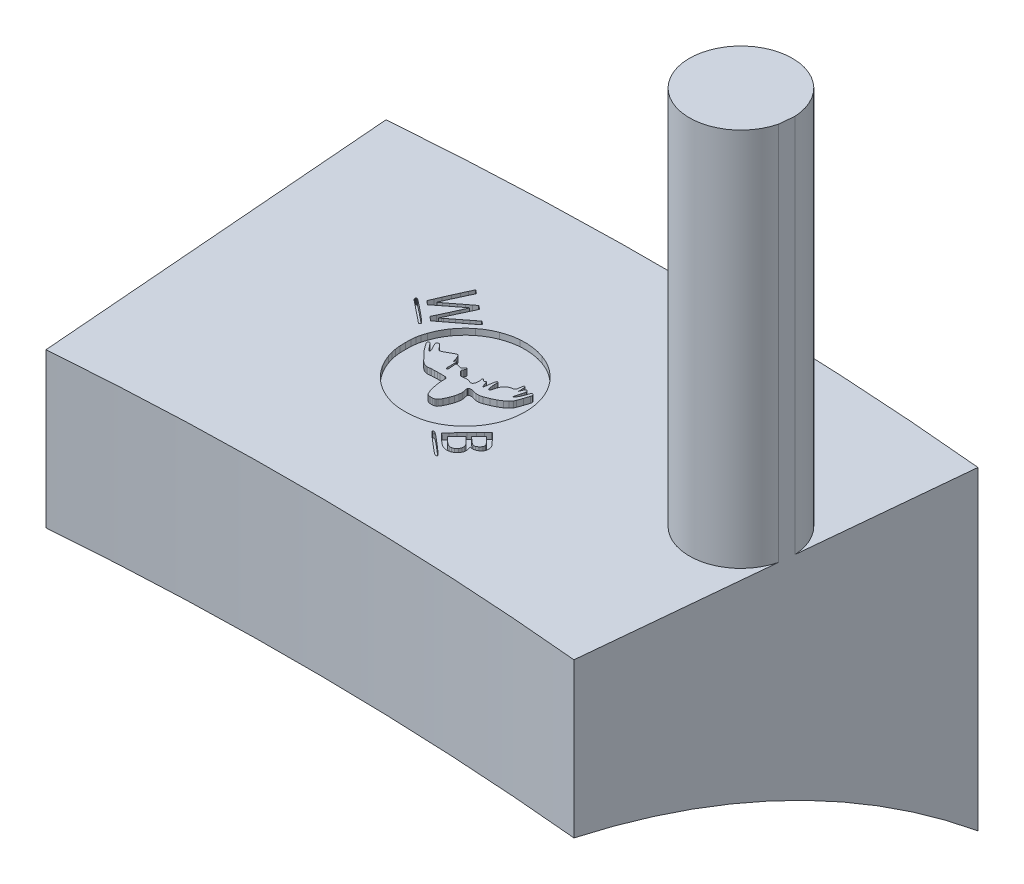
SolidWorks part; units mm, degrees
ref_plane "Front Plane" through (0, 0, 0) normal (0, 0, 1) x (1, 0, 0)
ref_plane "Top Plane" through (0, 0, 0) normal (0, 1, 0) x (1, 0, 0)
ref_plane "Right Plane" through (0, 0, 0) normal (1, 0, 0) x (0, 0, -1)
sketch "Sketch1" plane through (0, 0, 0) normal (0, 1, 0) x (1, 0, 0)
  circle A0 centre (0, 0) radius 140.97
  circle A1 centre (0, 0) radius 125.73
  dimension "D1" = 281.94
  dimension "D2" = 251.46
extrude "Boss-Extrude1" add sketch "Sketch1" along normal blind 12.954
sketch "Sketch3" plane through (0, 12.954, 0) normal (0, 1, 0) x (1, 0, 0)
  line L0 (0, 0) -> (13.4916, 140.3229)
  line L1 (13.4916, 140.3229) -> (0, 0)
  line L2 (0, 0) -> (-11.0802, 140.5339)
  circle A0 centre (0, 0) radius 140.97 construction
  circle A1 centre (0, 0) radius 140.97
  circle M3 centre (0, 0) radius 140.97
  circle M4 centre (0, 0) radius 125.73
  dimension "D1" = 10
extrude "Cut-Extrude1" cut sketch "Sketch3" against normal blind 12.954 contours L0 L2 M4 | L2 L0 M4 M3 region at (-0.0205, 12.954, 2.3917) region at (16.7282, 12.954, -132.3566)
sketch "Sketch5" plane through (0, 0, 0) normal (0, 1, 0) x (1, 0, 0)
  line L0 (-9.8823, 125.341) -> (-11.0802, 140.5339) construction
  line L1 (12.033, 125.1529) -> (13.4916, 140.3229) construction
  arc A1 (-10.4813, 132.9374) -> (12.7623, 132.7379) centre (0, 0) cw
  circle A2 centre (10.7123, 133.3451) radius 2.1209
  dimension "D1" = 4.2418
  dimension "D2" = 2.05
  dimension "D3" = 133.35
extrude "Boss-Extrude2" add sketch "Sketch5" along normal blind 28.575 contours A2
sketch "Sketch2" plane through (0, 0, 0) normal (0, 0, 1) x (1, 0, 0)
  line L0 (0, 12.954) -> (-125.73, 12.954)
  line L1 (13.4916, 12.954) -> (-11.0802, 12.954) construction
  line L2 (-125.73, 12.954) -> (-125.73, 6.604)
  line L3 (-125.73, 6.604) -> (-125.73, 0)
  line L4 (-125.73, 0) -> (-140.97, 0)
  line L5 (0, 0) -> (0, 30.8515)
  arc A0 (-125.73, 6.604) -> (-140.97, 0) centre (-121.1655, -24.8162) ccw
  dimension "D3" = 31.75
  dimension "D1" = 125.73
  dimension "D2" = 6.35
revolve "Cut-Revolve1" cut sketch "Sketch2" angle 360 about L5
sketch "Sketch6" plane through (0, 0, 0) normal (0.9954, 0, 0.0957) x (0.0957, 0, -0.9954)
  line L1 (114.9487, -1.4366) -> (150.8904, -1.4366)
  line L2 (114.9487, -1.4366) -> (114.9487, 48.5634)
  line L3 (114.9487, 48.5634) -> (150.8904, 48.5634)
  line L4 (150.8904, -1.4366) -> (150.8904, 48.5634)
  dimension "D1" = 50
extrude "Cut-Extrude2" cut sketch "Sketch6" along normal blind 25.4
sketch "Sketch7" plane through (0, 12.954, 0) normal (0, 1, 0) x (1, 0, 0)
  line L0 (-3.7053, 134.8491) -> (-3.6341, 134.7927)
  line L1 (-3.6341, 134.7927) -> (-3.1603, 135.1619)
  line L2 (-3.1603, 135.1619) -> (-2.9772, 135.3047)
  line L3 (-2.9772, 135.3047) -> (-2.8193, 135.4277)
  line L4 (-2.8193, 135.4277) -> (-2.6815, 135.5351)
  line L5 (-2.6815, 135.5351) -> (-2.6645, 135.5483)
  line L6 (-3.081, 134.6146) -> (-3.1693, 134.4272)
  line L7 (-3.1693, 134.4272) -> (-3.0827, 134.3548)
  line L8 (-3.0827, 134.3548) -> (-2.9962, 134.2823)
  line L9 (-2.9962, 134.2823) -> (-2.4199, 134.7222)
  line L10 (-2.6915, 134.7377) -> (-2.8183, 134.6385)
  line L11 (-2.8652, 134.6025) -> (-2.9338, 134.5503)
  line L12 (-2.9338, 134.5503) -> (-2.8718, 134.6853)
  line L13 (-2.8359, 134.7632) -> (-2.7678, 134.9098)
  line L14 (-2.7678, 134.9098) -> (-2.6878, 135.0818)
  line L15 (-2.6878, 135.0818) -> (-2.6046, 135.26)
  line L16 (-2.6046, 135.26) -> (-2.3995, 135.6997)
  line L17 (-2.3995, 135.6997) -> (-2.4697, 135.7591)
  line L18 (-3.3944, 135.1758) -> (-3.5283, 135.0739)
  line L19 (-3.534, 135.0793) -> (-3.4641, 135.2346)
  line L20 (-3.2799, 135.6368) -> (-3.0213, 136.1941)
  line L21 (-3.0213, 136.1941) -> (-3.0907, 136.254)
  line L22 (-3.1779, 136.3098) -> (-3.2698, 136.1122)
  line L23 (1.3179, 133.7284) -> (1.327, 133.5741)
  line L24 (1.327, 133.5741) -> (1.3617, 133.6657)
  line L25 (-1.9323, 133.5887) -> (-1.9076, 133.5586)
  line L26 (-1.9076, 133.5586) -> (-1.8767, 133.521)
  line L27 (-1.8767, 133.521) -> (-1.8472, 133.485)
  line L28 (-0.9298, 133.0884) -> (-0.9418, 133.2717)
  line L29 (-0.9418, 133.2717) -> (-0.8956, 133.2717)
  line L30 (-0.5709, 133.2146) -> (-0.6086, 133.1406)
  line L31 (-0.6086, 133.1406) -> (-0.5415, 133.0587)
  line L32 (2.3359, 130.5324) -> (2.3094, 130.596)
  line L33 (2.3094, 130.596) -> (2.4047, 130.5856)
  line L34 (2.2433, 131.5638) -> (2.0938, 131.4139)
  line L35 (2.0965, 130.8858) -> (1.9736, 131.0016)
  line L36 (1.9736, 131.0016) -> (2.0164, 131.0508)
  line L37 (1.6081, 130.3734) -> (1.4737, 130.5022)
  line L38 (1.4737, 130.5022) -> (1.6657, 130.6956)
  line L39 (1.6657, 130.6956) -> (1.8577, 130.8889)
  line L40 (1.8577, 130.8889) -> (1.9656, 130.7837)
  arc A0 (-3.4904, 135.6272) -> (-3.6076, 135.3626) centre (27.6931, 121.6549) ccw
  arc A1 (-3.6076, 135.3626) -> (-3.7046, 135.137) centre (12.6966, 128.2224) ccw
  arc A2 (-3.7046, 135.137) -> (-3.7885, 134.9374) centre (82.6018, 98.751) ccw
  arc A3 (-3.7885, 134.9374) -> (-3.7873, 134.9229) centre (-3.7738, 134.9313) ccw
  arc A4 (-3.7873, 134.9229) -> (-3.7794, 134.9132) centre (-3.7452, 134.9489) ccw
  arc A5 (-3.7794, 134.9132) -> (-3.7588, 134.894) centre (-3.121, 135.602) ccw
  arc A6 (-3.7588, 134.894) -> (-3.7334, 134.8719) centre (-3.1178, 135.6055) ccw
  arc A7 (-3.7334, 134.8719) -> (-3.7053, 134.8491) centre (-2.9112, 135.8517) ccw
  arc A8 (-2.6578, 135.5431) -> (-2.6645, 135.5483) centre (-2.6618, 135.5449) ccw
  arc A9 (-2.7745, 135.2804) -> (-2.6578, 135.5431) centre (-77.3531, 168.543) ccw
  arc A10 (-2.9131, 134.9747) -> (-2.7745, 135.2804) centre (-26.7146, 145.9578) ccw
  arc A11 (-3.081, 134.6146) -> (-2.9131, 134.9747) centre (-49.4562, 156.4518) ccw
  arc A12 (-2.4199, 134.7222) -> (-2.197, 134.8928) centre (-70.4269, 223.8204) ccw
  arc A13 (-2.197, 134.8928) -> (-2.0048, 135.0409) centre (-40.4648, 184.7692) ccw
  arc A14 (-2.0048, 135.0409) -> (-1.8382, 135.1699) centre (-111.6015, 276.7477) ccw
  arc A15 (-1.8382, 135.1699) -> (-1.816, 135.1893) centre (-1.9902, 135.366) ccw
  arc A16 (-1.816, 135.1893) -> (-1.804, 135.2061) centre (-1.8581, 135.232) ccw
  arc A17 (-1.804, 135.2061) -> (-1.8039, 135.2208) centre (-1.8197, 135.2136) ccw
  arc A18 (-1.8039, 135.2208) -> (-1.8165, 135.2382) centre (-1.853, 135.1984) ccw
  arc A19 (-1.8165, 135.2382) -> (-1.8527, 135.2698) centre (-2.4989, 134.4947) ccw
  arc A20 (-1.8527, 135.2698) -> (-1.8782, 135.2903) centre (-2.4241, 134.5844) ccw
  arc A21 (-1.8782, 135.2903) -> (-1.902, 135.3077) centre (-2.2326, 134.8321) ccw
  arc A22 (-1.902, 135.3077) -> (-1.9222, 135.3212) centre (-2.2752, 134.7707) ccw
  arc A23 (-1.9222, 135.3212) -> (-1.9303, 135.3238) centre (-1.9309, 135.3076) ccw
  arc A24 (-1.9303, 135.3238) -> (-1.94, 135.3207) centre (-1.9309, 135.3087) ccw
  arc A25 (-1.94, 135.3207) -> (-2.0651, 135.2258) centre (61.9876, 50.9611) ccw
  arc A26 (-2.0651, 135.2258) -> (-2.2057, 135.1178) centre (8.9255, 120.7671) ccw
  arc A27 (-2.2057, 135.1178) -> (-2.3702, 134.9895) centre (19.016, 107.7582) ccw
  arc A28 (-2.5385, 134.8574) -> (-2.3702, 134.9895) centre (-141.7495, 312.4628) ccw
  arc A29 (-2.6915, 134.7377) -> (-2.5385, 134.8574) centre (-97.35, 255.8182) ccw
  arc A30 (-2.8652, 134.6025) -> (-2.8183, 134.6385) centre (-5.5175, 138.0943) ccw
  arc A31 (-2.8359, 134.7632) -> (-2.8718, 134.6853) centre (16.7108, 125.6919) ccw
  arc A32 (-2.4697, 135.7591) -> (-2.4976, 135.7819) centre (-3.1441, 134.9621) ccw
  arc A33 (-2.4976, 135.7819) -> (-2.5233, 135.8012) centre (-2.9068, 135.263) ccw
  arc A34 (-2.5233, 135.8012) -> (-2.5452, 135.8163) centre (-2.9811, 135.1588) ccw
  arc A35 (-2.5452, 135.8163) -> (-2.5535, 135.8188) centre (-2.5538, 135.8033) ccw
  arc A36 (-2.5535, 135.8188) -> (-2.5632, 135.8157) centre (-2.5538, 135.8033) ccw
  arc A37 (-2.5632, 135.8157) -> (-2.7041, 135.7088) centre (89.1723, 14.6991) ccw
  arc A38 (-2.7041, 135.7088) -> (-2.8622, 135.5877) centre (11.3945, 117.1401) ccw
  arc A39 (-2.8622, 135.5877) -> (-3.0473, 135.4439) centre (24.4097, 100.2988) ccw
  arc A40 (-3.2319, 135.3004) -> (-3.0473, 135.4439) centre (-33.5628, 174.5039) ccw
  arc A41 (-3.3944, 135.1758) -> (-3.2319, 135.3004) centre (-18.5883, 155.149) ccw
  arc A42 (-3.533, 135.0742) -> (-3.5283, 135.0739) centre (-3.5305, 135.0767) ccw
  arc A43 (-3.534, 135.0793) -> (-3.533, 135.0742) centre (-3.5298, 135.0774) ccw
  arc A44 (-3.3787, 135.4228) -> (-3.4641, 135.2346) centre (21.2653, 124.1192) ccw
  arc A45 (-3.2799, 135.6368) -> (-3.3787, 135.4228) centre (45.0105, 113.2279) ccw
  arc A46 (-3.0907, 136.254) -> (-3.1181, 136.277) centre (-3.8659, 135.3572) ccw
  arc A47 (-3.1181, 136.277) -> (-3.143, 136.2963) centre (-3.5733, 135.7171) ccw
  arc A48 (-3.143, 136.2963) -> (-3.1643, 136.3117) centre (-3.7204, 135.5191) ccw
  arc A49 (-3.1643, 136.3117) -> (-3.1714, 136.3139) centre (-3.1714, 136.3016) ccw
  arc A50 (-3.1714, 136.3139) -> (-3.1779, 136.3098) centre (-3.1714, 136.3068) ccw
  arc A51 (-3.2698, 136.1122) -> (-3.3716, 135.8905) centre (22.7128, 124.0411) ccw
  arc A52 (-3.3716, 135.8905) -> (-3.4904, 135.6272) centre (47.6402, 112.7173) ccw
  arc A53 (-0.4782, 135.4512) -> (-1.1743, 135.2907) centre (-0.2887, 133.0396) ccw
  arc A54 (-1.1743, 135.2907) -> (-1.7996, 134.9331) centre (-0.2599, 132.9664) ccw
  arc A55 (-1.7996, 134.9331) -> (-2.297, 134.4119) centre (-0.2587, 132.9648) ccw
  arc A56 (-2.297, 134.4119) -> (-2.6206, 133.7741) centre (-0.318, 133.0069) ccw
  arc A57 (-2.6206, 133.7741) -> (-2.6816, 133.5704) centre (0.7096, 132.6645) ccw
  arc A58 (-2.6816, 133.5704) -> (-2.7175, 133.3995) centre (-1.1276, 133.1553) ccw
  arc A59 (-2.7175, 133.3995) -> (-2.7356, 133.22) centre (-0.9884, 133.1339) ccw
  arc A60 (-2.7356, 133.22) -> (-2.7414, 132.9876) centre (2.001, 132.9866) ccw
  arc A61 (-2.7414, 132.9876) -> (-2.7342, 132.7515) centre (1.1347, 132.9867) ccw
  arc A62 (-2.7342, 132.7515) -> (-2.7122, 132.5515) centre (-0.6881, 132.8759) ccw
  arc A63 (-2.7122, 132.5515) -> (-2.6719, 132.3634) centre (-0.89, 132.8435) ccw
  arc A64 (-2.6719, 132.3634) -> (-2.6095, 132.1645) centre (-0.2052, 133.028) ccw
  arc A65 (-2.6095, 132.1645) -> (-2.3618, 131.6611) centre (-0.2566, 133.0096) ccw
  arc A66 (-2.3618, 131.6611) -> (-2.0077, 131.2245) centre (-0.2397, 133.0205) ccw
  arc A67 (-2.0077, 131.2245) -> (-1.5672, 130.8789) centre (-0.2538, 133.0061) ccw
  arc A68 (-1.5672, 130.8789) -> (-1.0646, 130.6436) centre (-0.2999, 132.9314) ccw
  arc A69 (-1.0646, 130.6436) -> (-0.869, 130.586) centre (-0.1744, 133.3069) ccw
  arc A70 (-0.869, 130.586) -> (-0.6883, 130.5492) centre (-0.4028, 132.4122) ccw
  arc A71 (-0.6883, 130.5492) -> (-0.4985, 130.5291) centre (-0.3795, 132.5646) ccw
  arc A72 (-0.4985, 130.5291) -> (-0.2751, 130.5226) centre (-0.2751, 134.3484) ccw
  arc A73 (-0.2751, 130.5226) -> (0.2204, 130.568) centre (-0.2751, 133.2471) ccw
  arc A74 (0.2204, 130.568) -> (0.6763, 130.7029) centre (-0.1935, 132.806) ccw
  arc A75 (0.6763, 130.7029) -> (1.0934, 130.9291) centre (-0.1898, 132.797) ccw
  arc A76 (1.0934, 130.9291) -> (1.4737, 131.2459) centre (-0.422, 133.135) ccw
  arc A77 (1.4737, 131.2459) -> (1.7714, 131.6037) centre (-0.3687, 133.0819) ccw
  arc A78 (1.7714, 131.6037) -> (1.9919, 132.0001) centre (-0.1592, 132.9372) ccw
  arc A79 (1.9919, 132.0001) -> (2.1323, 132.4321) centre (-0.167, 132.9406) ccw
  arc A80 (2.1323, 132.4321) -> (2.1925, 132.896) centre (-0.4472, 133.0025) ccw
  arc A81 (2.1925, 132.896) -> (2.0159, 133.9153) centre (-0.265, 132.9952) ccw
  arc A82 (2.0159, 133.9153) -> (1.4357, 134.7717) centre (-0.2634, 132.9958) ccw
  arc A83 (1.4357, 134.7717) -> (0.5531, 135.3152) centre (-0.2723, 132.9865) ccw
  arc A84 (0.5531, 135.3152) -> (-0.4782, 135.4512) centre (-0.2823, 132.9582) ccw
  arc A85 (1.4006, 133.7596) -> (1.3617, 133.6657) centre (2.8754, 133.0934) ccw
  arc A86 (1.4296, 133.7958) -> (1.4006, 133.7596) centre (1.4853, 133.7214) ccw
  arc A87 (1.458, 133.796) -> (1.4296, 133.7958) centre (1.444, 133.7766) ccw
  arc A88 (1.4902, 133.7619) -> (1.458, 133.796) centre (1.3832, 133.6929) ccw
  arc A89 (1.5027, 133.7326) -> (1.4902, 133.7619) centre (1.4113, 133.711) ccw
  arc A90 (1.505, 133.7003) -> (1.5027, 133.7326) centre (1.404, 133.7093) ccw
  arc A91 (1.497, 133.6519) -> (1.505, 133.7003) centre (1.1888, 133.7284) ccw
  arc A92 (1.4719, 133.5557) -> (1.497, 133.6519) centre (-2.7581, 134.7073) ccw
  arc A93 (1.4719, 133.5557) -> (1.4199, 133.3622) centre (32.8353, 125.0172) ccw
  arc A94 (1.4199, 133.3622) -> (1.4061, 133.2971) centre (2.0492, 133.1951) ccw
  arc A95 (1.4061, 133.2971) -> (1.411, 133.2751) centre (1.4365, 133.2922) ccw
  arc A96 (1.411, 133.2751) -> (1.4268, 133.2711) centre (1.4211, 133.2818) ccw
  arc A97 (1.4268, 133.2711) -> (1.4647, 133.307) centre (1.38, 133.3585) ccw
  arc A98 (1.4647, 133.307) -> (1.5179, 133.4023) centre (0.2193, 134.064) ccw
  arc A99 (1.5179, 133.4023) -> (1.57, 133.5164) centre (0.2191, 134.0641) ccw
  arc A100 (1.57, 133.5164) -> (1.6108, 133.6322) centre (0.3339, 134.0176) ccw
  arc A101 (1.6282, 133.6837) -> (1.6108, 133.6322) centre (2.4219, 133.3874) ccw
  arc A102 (1.6472, 133.7285) -> (1.6282, 133.6837) centre (2.14, 133.4926) ccw
  arc A103 (1.6656, 133.7632) -> (1.6472, 133.7285) centre (2.0811, 133.5208) ccw
  arc A104 (1.6789, 133.7745) -> (1.6656, 133.7632) centre (1.6884, 133.7499) ccw
  arc A105 (1.7048, 133.7765) -> (1.6789, 133.7745) centre (1.6953, 133.732) ccw
  arc A106 (1.7312, 133.7646) -> (1.7048, 133.7765) centre (1.6905, 133.71) ccw
  arc A107 (1.7507, 133.7424) -> (1.7312, 133.7646) centre (1.6884, 133.7071) ccw
  arc A108 (1.7577, 133.716) -> (1.7507, 133.7424) centre (1.704, 133.716) ccw
  arc A109 (1.7473, 133.6491) -> (1.7577, 133.716) centre (1.5384, 133.716) ccw
  arc A110 (1.6762, 133.4326) -> (1.7473, 133.6491) centre (-12.9634, 138.3588) ccw
  arc A111 (1.6029, 133.2211) -> (1.6762, 133.4326) centre (-9.8458, 137.3098) ccw
  arc A112 (1.5651, 133.1434) -> (1.6029, 133.2211) centre (1.231, 133.3539) ccw
  arc A113 (1.4769, 133.0352) -> (1.5651, 133.1434) centre (1.0778, 133.4505) ccw
  arc A114 (1.3504, 132.9308) -> (1.4769, 133.0352) centre (0.7216, 133.8211) ccw
  arc A115 (1.1873, 132.8307) -> (1.3504, 132.9308) centre (0.4927, 134.1452) ccw
  arc A116 (0.988, 132.7358) -> (1.1873, 132.8307) centre (-0.0385, 135.1505) ccw
  arc A117 (0.7819, 132.6544) -> (0.988, 132.7358) centre (-0.7162, 136.7447) ccw
  arc A118 (0.6553, 132.6235) -> (0.7819, 132.6544) centre (0.5817, 133.2012) ccw
  arc A119 (0.5384, 132.6249) -> (0.6553, 132.6235) centre (0.602, 133.0416) ccw
  arc A120 (0.3782, 132.6581) -> (0.5384, 132.6249) centre (0.7728, 134.1615) ccw
  arc A121 (0.3782, 132.6581) -> (0.3121, 132.674) centre (-0.0318, 131.0961) ccw
  arc A122 (0.3121, 132.674) -> (0.2692, 132.68) centre (0.2509, 132.3933) ccw
  arc A123 (0.2692, 132.68) -> (0.2366, 132.6783) centre (0.2602, 132.5394) ccw
  arc A124 (0.2366, 132.6783) -> (0.2065, 132.669) centre (0.257, 132.5581) ccw
  arc A125 (0.2065, 132.669) -> (0.1809, 132.6549) centre (0.285, 132.4967) ccw
  arc A126 (0.1809, 132.6549) -> (0.1693, 132.641) centre (0.1981, 132.6287) ccw
  arc A127 (0.1693, 132.641) -> (0.1665, 132.622) centre (0.2041, 132.6262) ccw
  arc A128 (0.1665, 132.622) -> (0.1722, 132.5884) centre (0.4797, 132.6573) ccw
  arc A129 (0.1967, 132.4711) -> (0.1722, 132.5884) centre (-3.9257, 131.6698) ccw
  arc A130 (0.2063, 132.3993) -> (0.1967, 132.4711) centre (-0.4048, 132.3542) ccw
  arc A131 (0.2062, 132.3361) -> (0.2063, 132.3993) centre (-0.2091, 132.3686) ccw
  arc A132 (0.1968, 132.2545) -> (0.2062, 132.3361) centre (-0.9505, 132.4267) ccw
  arc A133 (0.1627, 132.1026) -> (0.1968, 132.2545) centre (-0.8743, 132.4153) ccw
  arc A134 (0.1025, 131.9318) -> (0.1627, 132.1026) centre (-1.722, 132.6709) ccw
  arc A135 (0.0281, 131.7701) -> (0.1025, 131.9318) centre (-1.6818, 132.6546) ccw
  arc A136 (-0.0494, 131.6465) -> (0.0281, 131.7701) centre (-0.7526, 132.1739) ccw
  arc A137 (-0.0765, 131.6158) -> (-0.0494, 131.6465) centre (-0.2547, 131.8004) ccw
  arc A138 (-0.1032, 131.5969) -> (-0.0765, 131.6158) centre (-0.1515, 131.6935) ccw
  arc A139 (-0.1376, 131.5849) -> (-0.1032, 131.5969) centre (-0.1672, 131.7249) ccw
  arc A140 (-0.1905, 131.5761) -> (-0.1376, 131.5849) centre (-0.2697, 132.2102) ccw
  arc A141 (-0.2337, 131.5728) -> (-0.1905, 131.5761) centre (-0.2463, 132.0233) ccw
  arc A142 (-0.2812, 131.5732) -> (-0.2337, 131.5728) centre (-0.2517, 132.2155) ccw
  arc A143 (-0.3263, 131.577) -> (-0.2812, 131.5732) centre (-0.2536, 132.1743) ccw
  arc A144 (-0.3622, 131.5839) -> (-0.3263, 131.577) centre (-0.2952, 131.8327) ccw
  arc A145 (-0.4054, 131.5994) -> (-0.3622, 131.5839) centre (-0.287, 131.863) ccw
  arc A146 (-0.4327, 131.6188) -> (-0.4054, 131.5994) centre (-0.3703, 131.6776) ccw
  arc A147 (-0.4556, 131.6512) -> (-0.4327, 131.6188) centre (-0.3292, 131.7162) ccw
  arc A148 (-0.4871, 131.7167) -> (-0.4556, 131.6512) centre (0.7581, 132.2755) ccw
  arc A149 (-0.535, 131.851) -> (-0.4871, 131.7167) centre (0.331, 132.0838) ccw
  arc A150 (-0.5802, 132.043) -> (-0.535, 131.851) centre (2.5348, 132.6762) ccw
  arc A151 (-0.6139, 132.2401) -> (-0.5802, 132.043) centre (2.5486, 132.679) ccw
  arc A152 (-0.6246, 132.393) -> (-0.6139, 132.2401) centre (0.4991, 132.3946) ccw
  arc A153 (-0.6246, 132.393) -> (-0.6321, 132.5254) centre (-1.831, 132.3914) ccw
  arc A154 (-0.6321, 132.5254) -> (-0.6629, 132.5766) centre (-0.7032, 132.5175) ccw
  arc A155 (-0.6629, 132.5766) -> (-0.7297, 132.5986) centre (-0.7341, 132.4722) ccw
  arc A156 (-0.7297, 132.5986) -> (-0.9303, 132.6016) centre (-0.9077, 127.4872) ccw
  arc A157 (-0.9303, 132.6016) -> (-1.0381, 132.6001) centre (-0.9059, 127.0686) ccw
  arc A158 (-1.0381, 132.6001) -> (-1.1527, 132.5964) centre (-0.8698, 125.5587) ccw
  arc A159 (-1.1527, 132.5964) -> (-1.2574, 132.5913) centre (-0.8962, 126.2158) ccw
  arc A160 (-1.2574, 132.5913) -> (-1.3315, 132.5855) centre (-1.1633, 130.9302) ccw
  arc A161 (-1.4163, 132.5786) -> (-1.3315, 132.5855) centre (-1.548, 134.7162) ccw
  arc A162 (-1.4685, 132.5795) -> (-1.4163, 132.5786) centre (-1.4366, 132.9084) ccw
  arc A163 (-1.5122, 132.5884) -> (-1.4685, 132.5795) centre (-1.4479, 132.792) ccw
  arc A164 (-1.5641, 132.608) -> (-1.5122, 132.5884) centre (-1.3611, 133.0669) ccw
  arc A165 (-1.6022, 132.6284) -> (-1.5641, 132.608) centre (-1.4479, 132.8706) ccw
  arc A166 (-1.6472, 132.6596) -> (-1.6022, 132.6284) centre (-1.2155, 133.2353) ccw
  arc A167 (-1.6915, 132.6954) -> (-1.6472, 132.6596) centre (-1.1914, 133.2674) ccw
  arc A168 (-1.7279, 132.7308) -> (-1.6915, 132.6954) centre (-1.3743, 133.0581) ccw
  arc A169 (-1.7279, 132.7308) -> (-1.7683, 132.7737) centre (-4.2716, 130.3758) ccw
  arc A170 (-1.7683, 132.7737) -> (-1.8274, 132.8351) centre (-12.2621, 122.7219) ccw
  arc A171 (-1.8274, 132.8351) -> (-1.893, 132.9024) centre (-13.4111, 121.6083) ccw
  arc A172 (-1.893, 132.9024) -> (-1.9558, 132.966) centre (-11.3435, 123.6357) ccw
  arc A173 (-2.0684, 133.0909) -> (-1.9558, 132.966) centre (-0.7314, 134.183) ccw
  arc A174 (-2.1879, 133.2468) -> (-2.0684, 133.0909) centre (0.4124, 135.1172) ccw
  arc A175 (-2.2925, 133.3983) -> (-2.1879, 133.2468) centre (1.5666, 135.9475) ccw
  arc A176 (-2.3109, 133.4596) -> (-2.2925, 133.3983) centre (-2.1998, 133.4596) ccw
  arc A177 (-2.3085, 133.4712) -> (-2.3109, 133.4596) centre (-2.2812, 133.4596) ccw
  arc A178 (-2.3015, 133.483) -> (-2.3085, 133.4712) centre (-2.261, 133.451) ccw
  arc A179 (-2.2911, 133.4932) -> (-2.3015, 133.483) centre (-2.2564, 133.4473) ccw
  arc A180 (-2.2788, 133.5) -> (-2.2911, 133.4932) centre (-2.2609, 133.4532) ccw
  arc A181 (-2.2516, 133.4993) -> (-2.2788, 133.5) centre (-2.2661, 133.4667) ccw
  arc A182 (-2.2217, 133.4789) -> (-2.2516, 133.4993) centre (-2.2928, 133.4065) ccw
  arc A183 (-2.1747, 133.4274) -> (-2.2217, 133.4789) centre (-2.6697, 133.0231) ccw
  arc A184 (-2.0566, 133.2816) -> (-2.1747, 133.4274) centre (-19.5072, 119.2709) ccw
  arc A185 (-2.0566, 133.2816) -> (-1.9644, 133.1811) centre (-1.2577, 133.923) ccw
  arc A186 (-1.9644, 133.1811) -> (-1.935, 133.193) centre (-1.9524, 133.1937) ccw
  arc A187 (-1.935, 133.193) -> (-1.9527, 133.279) centre (-2.1154, 133.2006) ccw
  arc A188 (-1.9527, 133.279) -> (-2.0488, 133.4663) centre (-5.75, 131.4486) ccw
  arc A189 (-2.0881, 133.5472) -> (-2.0488, 133.4663) centre (-1.2179, 133.9193) ccw
  arc A190 (-2.0971, 133.5973) -> (-2.0881, 133.5472) centre (-1.9836, 133.5919) ccw
  arc A191 (-2.0809, 133.6297) -> (-2.0971, 133.5973) centre (-2.0525, 133.5952) ccw
  arc A192 (-2.04, 133.6503) -> (-2.0809, 133.6297) centre (-2.0145, 133.549) ccw
  arc A193 (-2.015, 133.6537) -> (-2.04, 133.6503) centre (-2.0126, 133.5413) ccw
  arc A194 (-1.9949, 133.65) -> (-2.015, 133.6537) centre (-2.0139, 133.6026) ccw
  arc A195 (-1.976, 133.6382) -> (-1.9949, 133.65) centre (-2.0184, 133.5915) ccw
  arc A196 (-1.9549, 133.6161) -> (-1.976, 133.6382) centre (-2.1206, 133.4789) ccw
  arc A197 (-1.9323, 133.5887) -> (-1.9549, 133.6161) centre (-10.318, 126.689) ccw
  arc A198 (-1.8472, 133.485) -> (-1.815, 133.4488) centre (-1.3879, 133.861) ccw
  arc A199 (-1.815, 133.4488) -> (-1.7852, 133.4221) centre (-1.6164, 133.6404) ccw
  arc A200 (-1.7852, 133.4221) -> (-1.7588, 133.4052) centre (-1.6788, 133.5597) ccw
  arc A201 (-1.7588, 133.4052) -> (-1.7372, 133.4) centre (-1.7373, 133.4467) ccw
  arc A202 (-1.7372, 133.4) -> (-1.7118, 133.4055) centre (-1.7373, 133.4623) ccw
  arc A203 (-1.7118, 133.4055) -> (-1.6442, 133.4371) centre (-2.7852, 135.7907) ccw
  arc A204 (-1.6442, 133.4371) -> (-1.5642, 133.4779) centre (-2.6243, 135.4588) ccw
  arc A205 (-1.5642, 133.4779) -> (-1.477, 133.5262) centre (-3.1724, 136.483) ccw
  arc A206 (-1.3638, 133.5895) -> (-1.477, 133.5262) centre (1.5912, 128.1754) ccw
  arc A207 (-1.2955, 133.6227) -> (-1.3638, 133.5895) centre (-0.9785, 132.8837) ccw
  arc A208 (-1.2505, 133.638) -> (-1.2955, 133.6227) centre (-1.1763, 133.3448) ccw
  arc A209 (-1.2238, 133.6348) -> (-1.2505, 133.638) centre (-1.2413, 133.6016) ccw
  arc A210 (-1.1941, 133.607) -> (-1.2238, 133.6348) centre (-1.2594, 133.567) ccw
  arc A211 (-1.1596, 133.5429) -> (-1.1941, 133.607) centre (-1.7605, 133.2604) ccw
  arc A212 (-1.1289, 133.4664) -> (-1.1596, 133.5429) centre (-1.8056, 133.2393) ccw
  arc A213 (-1.1093, 133.3913) -> (-1.1289, 133.4664) centre (-1.6607, 133.2879) ccw
  arc A214 (-1.1093, 133.3913) -> (-1.098, 133.3478) centre (-0.7919, 133.4509) ccw
  arc A215 (-1.098, 133.3478) -> (-1.0823, 133.3188) centre (-1.0067, 133.3785) ccw
  arc A216 (-1.0823, 133.3188) -> (-1.071, 133.3184) centre (-1.0765, 133.3234) ccw
  arc A217 (-1.071, 133.3184) -> (-1.0646, 133.3347) centre (-1.0887, 133.3347) ccw
  arc A218 (-1.0619, 133.3459) -> (-1.0646, 133.3347) centre (-1.0405, 133.3347) ccw
  arc A219 (-1.0542, 133.3551) -> (-1.0619, 133.3459) centre (-1.0367, 133.3327) ccw
  arc A220 (-1.0424, 133.3612) -> (-1.0542, 133.3551) centre (-1.0322, 133.327) ccw
  arc A221 (-1.028, 133.3633) -> (-1.0424, 133.3612) centre (-1.028, 133.3126) ccw
  arc A222 (-1.0077, 133.354) -> (-1.028, 133.3633) centre (-1.028, 133.3366) ccw
  arc A223 (-0.9966, 133.3301) -> (-1.0077, 133.354) centre (-1.0445, 133.3224) ccw
  arc A224 (-0.9921, 133.2772) -> (-0.9966, 133.3301) centre (-1.3528, 133.2731) ccw
  arc A225 (-0.9913, 133.1342) -> (-0.9921, 133.2772) centre (-13.6347, 133.1342) ccw
  arc A226 (-0.9913, 133.1342) -> (-0.9905, 132.9911) centre (11.7011, 133.1342) ccw
  arc A227 (-0.9905, 132.9911) -> (-0.986, 132.9383) centre (-0.6314, 132.9951) ccw
  arc A228 (-0.986, 132.9383) -> (-0.9749, 132.9144) centre (-0.9385, 132.9459) ccw
  arc A229 (-0.9749, 132.9144) -> (-0.9546, 132.9051) centre (-0.9546, 132.932) ccw
  arc A230 (-0.9546, 132.9051) -> (-0.9347, 132.9125) centre (-0.9546, 132.9354) ccw
  arc A231 (-0.9347, 132.9125) -> (-0.9247, 132.9311) centre (-0.9543, 132.935) ccw
  arc A232 (-0.9247, 132.9311) -> (-0.923, 132.9726) centre (-1.1463, 132.961) ccw
  arc A233 (-0.923, 132.9726) -> (-0.9298, 133.0884) centre (-9.6514, 132.5168) ccw
  arc A234 (-0.8725, 133.2698) -> (-0.8956, 133.2717) centre (-0.8956, 133.1272) ccw
  arc A235 (-0.84, 133.2636) -> (-0.8725, 133.2698) centre (-0.9646, 132.7006) ccw
  arc A236 (-0.8046, 133.2547) -> (-0.84, 133.2636) centre (-0.9797, 132.6327) ccw
  arc A237 (-0.7714, 133.2442) -> (-0.8046, 133.2547) centre (-0.9502, 132.7373) ccw
  arc A238 (-0.7714, 133.2442) -> (-0.7411, 133.2336) centre (0.5502, 136.9901) ccw
  arc A239 (-0.7411, 133.2336) -> (-0.7148, 133.2248) centre (-0.0054, 135.3739) ccw
  arc A240 (-0.7148, 133.2248) -> (-0.692, 133.2173) centre (0.9646, 138.3124) ccw
  arc A241 (-0.692, 133.2173) -> (-0.6881, 133.2167) centre (-0.6881, 133.2294) ccw
  arc A242 (-0.6881, 133.2167) -> (-0.685, 133.2183) centre (-0.6881, 133.2206) ccw
  arc A243 (-0.685, 133.2183) -> (-0.6727, 133.2355) centre (-1.8562, 134.0659) ccw
  arc A244 (-0.6727, 133.2355) -> (-0.6587, 133.2562) centre (-1.2471, 133.6385) ccw
  arc A245 (-0.6587, 133.2562) -> (-0.6431, 133.2808) centre (-1.7369, 133.9568) ccw
  arc A246 (-0.6103, 133.3209) -> (-0.6431, 133.2808) centre (-0.4757, 133.1774) ccw
  arc A247 (-0.5729, 133.3431) -> (-0.6103, 133.3209) centre (-0.5418, 133.2478) ccw
  arc A248 (-0.5457, 133.3396) -> (-0.5729, 133.3431) centre (-0.5629, 133.3126) ccw
  arc A249 (-0.5331, 133.3168) -> (-0.5457, 133.3396) centre (-0.5603, 133.3168) ccw
  arc A250 (-0.5354, 133.3013) -> (-0.5331, 133.3168) centre (-0.5864, 133.3168) ccw
  arc A251 (-0.5442, 133.2751) -> (-0.5354, 133.3013) centre (-0.9769, 133.4348) ccw
  arc A252 (-0.5564, 133.245) -> (-0.5442, 133.2751) centre (-1.0361, 133.4567) ccw
  arc A253 (-0.5709, 133.2146) -> (-0.5564, 133.245) centre (-1.1061, 133.4876) ccw
  arc A254 (-0.5415, 133.0587) -> (-0.4699, 132.9781) centre (0.5058, 133.9168) ccw
  arc A255 (-0.4699, 132.9781) -> (-0.4197, 132.9424) centre (-0.3507, 133.0928) ccw
  arc A256 (-0.4197, 132.9424) -> (-0.3664, 132.9322) centre (-0.372, 133.0463) ccw
  arc A257 (-0.3664, 132.9322) -> (-0.2888, 132.9427) centre (-0.3891, 133.3911) ccw
  arc A258 (-0.2119, 132.9545) -> (-0.2888, 132.9427) centre (-0.164, 132.385) ccw
  arc A259 (-0.1421, 132.9538) -> (-0.2119, 132.9545) centre (-0.1807, 132.5843) ccw
  arc A260 (-0.0767, 132.9403) -> (-0.1421, 132.9538) centre (-0.1772, 132.618) ccw
  arc A261 (-0.0127, 132.9139) -> (-0.0767, 132.9403) centre (-0.1923, 132.5696) ccw
  arc A262 (-0.0127, 132.9139) -> (0.0183, 132.8995) centre (0.16, 133.2449) ccw
  arc A263 (0.0183, 132.8995) -> (0.0384, 132.8954) centre (0.0389, 132.9496) ccw
  arc A264 (0.0384, 132.8954) -> (0.0569, 132.8994) centre (0.0388, 132.9386) ccw
  arc A265 (0.0569, 132.8994) -> (0.0815, 132.913) centre (-0.0238, 133.0738) ccw
  arc A266 (0.0815, 132.913) -> (0.1203, 132.9574) centre (0.0213, 133.0048) ccw
  arc A267 (0.1203, 132.9574) -> (0.146, 133.0326) centre (-0.1866, 133.1045) ccw
  arc A268 (0.146, 133.0326) -> (0.1549, 133.1189) centre (-0.2379, 133.1155) ccw
  arc A269 (0.1549, 133.1189) -> (0.143, 133.1978) centre (-0.1284, 133.1165) ccw
  arc A270 (0.1315, 133.2399) -> (0.143, 133.1978) centre (0.9676, 133.4448) ccw
  arc A271 (0.1291, 133.2635) -> (0.1315, 133.2399) centre (0.2153, 133.2605) ccw
  arc A272 (0.1339, 133.279) -> (0.1291, 133.2635) centre (0.1599, 133.2624) ccw
  arc A273 (0.1462, 133.2914) -> (0.1339, 133.279) centre (0.1681, 133.2572) ccw
  arc A274 (0.1605, 133.2962) -> (0.1462, 133.2914) centre (0.1631, 133.265) ccw
  arc A275 (0.175, 133.2937) -> (0.1605, 133.2962) centre (0.1629, 133.267) ccw
  arc A276 (0.191, 133.2828) -> (0.175, 133.2937) centre (0.1513, 133.2416) ccw
  arc A277 (0.2098, 133.2624) -> (0.191, 133.2828) centre (0.0311, 133.1166) ccw
  arc A278 (0.2098, 133.2624) -> (0.2333, 133.2354) centre (0.6565, 133.6272) ccw
  arc A279 (0.2333, 133.2354) -> (0.2462, 133.2281) centre (0.2514, 133.2522) ccw
  arc A280 (0.2462, 133.2281) -> (0.2587, 133.2308) centre (0.2494, 133.2431) ccw
  arc A281 (0.2587, 133.2308) -> (0.2781, 133.2477) centre (0.1476, 133.3782) ccw
  arc A282 (0.304, 133.2643) -> (0.2781, 133.2477) centre (0.3291, 133.1967) ccw
  arc A283 (0.3235, 133.2591) -> (0.304, 133.2643) centre (0.3101, 133.248) ccw
  arc A284 (0.3422, 133.2266) -> (0.3235, 133.2591) centre (0.239, 133.1888) ccw
  arc A285 (0.3762, 133.1298) -> (0.3422, 133.2266) centre (-3.3858, 131.8638) ccw
  arc A286 (0.3762, 133.1298) -> (0.3932, 133.0822) centre (1.6118, 133.5456) ccw
  arc A287 (0.3932, 133.0822) -> (0.4101, 133.0413) centre (1.1167, 133.3574) ccw
  arc A288 (0.4101, 133.0413) -> (0.4257, 133.0083) centre (1.2903, 133.435) ccw
  arc A289 (0.4257, 133.0083) -> (0.4336, 133.0013) centre (0.438, 133.0144) ccw
  arc A290 (0.4336, 133.0013) -> (0.4408, 133.0052) centre (0.4354, 133.0066) ccw
  arc A291 (0.4408, 133.0052) -> (0.4513, 133.0502) centre (-0.8578, 133.3328) ccw
  arc A292 (0.4513, 133.0502) -> (0.4618, 133.1068) centre (-0.5054, 133.2567) ccw
  arc A293 (0.4618, 133.1068) -> (0.4712, 133.1751) centre (-1.5138, 133.413) ccw
  arc A294 (0.4913, 133.3217) -> (0.4712, 133.1751) centre (4.7226, 132.6654) ccw
  arc A295 (0.5117, 133.417) -> (0.4913, 133.3217) centre (1.3333, 133.1911) ccw
  arc A296 (0.5334, 133.4758) -> (0.5117, 133.417) centre (0.8702, 133.3184) ccw
  arc A297 (0.5582, 133.4916) -> (0.5334, 133.4758) centre (0.5582, 133.4642) ccw
  arc A298 (0.5712, 133.4844) -> (0.5582, 133.4916) centre (0.5582, 133.4762) ccw
  arc A299 (0.5796, 133.4638) -> (0.5712, 133.4844) centre (0.518, 133.4507) ccw
  arc A300 (0.5845, 133.4259) -> (0.5796, 133.4638) centre (0.35, 133.4148) ccw
  arc A301 (0.5866, 133.3587) -> (0.5845, 133.4259) centre (-1.387, 133.3325) ccw
  arc A302 (0.5866, 133.3587) -> (0.5888, 133.3005) centre (1.7655, 133.3744) ccw
  arc A303 (0.5888, 133.3005) -> (0.594, 133.2353) centre (2.4548, 133.4177) ccw
  arc A304 (0.594, 133.2353) -> (0.6012, 133.1731) centre (2.3562, 133.408) ccw
  arc A305 (0.6012, 133.1731) -> (0.6095, 133.125) centre (1.2574, 133.2609) ccw
  arc A306 (0.6095, 133.125) -> (0.6219, 133.0729) centre (1.5738, 133.3273) ccw
  arc A307 (0.6219, 133.0729) -> (0.6336, 133.0444) centre (0.7392, 133.1042) ccw
  arc A308 (0.6336, 133.0444) -> (0.6477, 133.0296) centre (0.6695, 133.0647) ccw
  arc A309 (0.6477, 133.0296) -> (0.6666, 133.0242) centre (0.6666, 133.06) ccw
  arc A310 (0.6666, 133.0242) -> (0.6862, 133.0309) centre (0.6666, 133.0565) ccw
  arc A311 (0.6862, 133.0309) -> (0.7014, 133.0492) centre (0.6538, 133.0731) ccw
  arc A312 (0.7014, 133.0492) -> (0.7151, 133.0853) centre (0.5332, 133.1338) ccw
  arc A313 (0.7151, 133.0853) -> (0.7322, 133.1548) centre (-1.1384, 133.5794) ccw
  arc A314 (0.7851, 133.3152) -> (0.7322, 133.1548) centre (1.6, 132.9578) ccw
  arc A315 (0.8618, 133.4341) -> (0.7851, 133.3152) centre (1.1932, 133.1362) ccw
  arc A316 (0.964, 133.5131) -> (0.8618, 133.4341) centre (1.129, 133.1939) ccw
  arc A317 (1.0923, 133.5554) -> (0.964, 133.5131) centre (1.1601, 133.1337) ccw
  arc A318 (1.0923, 133.5554) -> (1.1549, 133.572) centre (1.0406, 133.877) ccw
  arc A319 (1.1549, 133.572) -> (1.1897, 133.5986) centre (1.1282, 133.643) ccw
  arc A320 (1.1897, 133.5986) -> (1.2094, 133.6449) centre (1.098, 133.6649) ccw
  arc A321 (1.2094, 133.6449) -> (1.2212, 133.7337) centre (0.2482, 133.8175) ccw
  arc A322 (1.2264, 133.7796) -> (1.2212, 133.7337) centre (2.0956, 133.6584) ccw
  arc A323 (1.2337, 133.822) -> (1.2264, 133.7796) centre (1.8873, 133.6875) ccw
  arc A324 (1.2419, 133.8569) -> (1.2337, 133.822) centre (1.8333, 133.6986) ccw
  arc A325 (1.2498, 133.8725) -> (1.2419, 133.8569) centre (1.2834, 133.8458) ccw
  arc A326 (1.2748, 133.8865) -> (1.2498, 133.8725) centre (1.2795, 133.8489) ccw
  arc A327 (1.2951, 133.8754) -> (1.2748, 133.8865) centre (1.2772, 133.8669) ccw
  arc A328 (1.3093, 133.8257) -> (1.2951, 133.8754) centre (1.1509, 133.8072) ccw
  arc A329 (1.3179, 133.7284) -> (1.3093, 133.8257) centre (-0.3953, 133.6267) ccw
  arc A330 (-4.1184, 134.7842) -> (-4.1219, 134.7727) centre (-4.0413, 134.7547) ccw
  arc A331 (-4.1219, 134.7727) -> (-4.1238, 134.7603) centre (-4.0269, 134.7514) ccw
  arc A332 (-4.1238, 134.7603) -> (-4.1241, 134.7489) centre (-4.0392, 134.7526) ccw
  arc A333 (-4.1241, 134.7489) -> (-4.1224, 134.7405) centre (-4.097, 134.7501) ccw
  arc A334 (-4.1224, 134.7405) -> (-4.0878, 134.6927) centre (-4.0177, 134.7799) ccw
  arc A335 (-4.0878, 134.6927) -> (-3.6357, 134.3298) centre (123.2171, 292.8162) ccw
  arc A336 (-3.6357, 134.3298) -> (-3.176, 133.9626) centre (186.271, 371.5942) ccw
  arc A337 (-3.176, 133.9626) -> (-3.139, 133.9534) centre (-3.1475, 133.9983) ccw
  arc A338 (-3.139, 133.9534) -> (-3.1267, 133.9586) centre (-3.1449, 133.9845) ccw
  arc A339 (-3.1267, 133.9586) -> (-3.1155, 133.969) centre (-3.1586, 134.004) ccw
  arc A340 (-3.1155, 133.969) -> (-3.1069, 133.983) centre (-3.1644, 134.0087) ccw
  arc A341 (-3.1069, 133.983) -> (-3.1025, 133.9983) centre (-3.1595, 134.0065) ccw
  arc A342 (-3.1025, 133.9983) -> (-3.1132, 134.0308) centre (-3.1406, 134.0038) ccw
  arc A343 (-3.1132, 134.0308) -> (-3.1918, 134.1064) centre (-4.582, 132.5823) ccw
  arc A344 (-3.1918, 134.1064) -> (-3.3227, 134.2206) centre (-5.7879, 131.2601) ccw
  arc A345 (-3.3227, 134.2206) -> (-3.5695, 134.4243) centre (-27.8822, 104.7271) ccw
  arc A346 (-3.5695, 134.4243) -> (-3.753, 134.5726) centre (-15.2353, 120.1749) ccw
  arc A347 (-3.753, 134.5726) -> (-3.9129, 134.6975) centre (-10.0598, 126.6644) ccw
  arc A348 (-3.9129, 134.6975) -> (-4.0524, 134.8035) centre (-20.7958, 112.634) ccw
  arc A349 (-4.0524, 134.8035) -> (-4.075, 134.8111) centre (-4.075, 134.7736) ccw
  arc A350 (-4.075, 134.8111) -> (-4.0884, 134.8091) centre (-4.075, 134.7655) ccw
  arc A351 (-4.0884, 134.8091) -> (-4.1014, 134.8032) centre (-4.0722, 134.7561) ccw
  arc A352 (-4.1014, 134.8032) -> (-4.112, 134.7945) centre (-4.0743, 134.7595) ccw
  arc A353 (-4.112, 134.7945) -> (-4.1184, 134.7842) centre (-4.0886, 134.7728) ccw
  arc A354 (1.7313, 131.0452) -> (1.5369, 130.8438) centre (26.1185, 107.3035) ccw
  arc A355 (1.5369, 130.8438) -> (1.3741, 130.6716) centre (14.2125, 118.7052) ccw
  arc A356 (1.3741, 130.6716) -> (1.2315, 130.5183) centre (76.8953, 60.2795) ccw
  arc A357 (1.2315, 130.5183) -> (1.2292, 130.5065) centre (1.2399, 130.5105) ccw
  arc A358 (1.2292, 130.5065) -> (1.2363, 130.4956) centre (1.2582, 130.5174) ccw
  arc A359 (1.2363, 130.4956) -> (1.2944, 130.4374) centre (11.8237, 141.0126) ccw
  arc A360 (1.2944, 130.4374) -> (1.3626, 130.3705) centre (5.59, 134.7518) ccw
  arc A361 (1.3626, 130.3705) -> (1.4424, 130.2943) centre (8.859, 138.1397) ccw
  arc A362 (1.4424, 130.2943) -> (1.6034, 130.1507) centre (4.0011, 133.001) ccw
  arc A363 (1.6034, 130.1507) -> (1.7224, 130.0677) centre (2.1193, 130.764) ccw
  arc A364 (1.7224, 130.0677) -> (1.8279, 130.0246) centre (1.9401, 130.4497) ccw
  arc A365 (1.8279, 130.0246) -> (1.941, 130.01) centre (1.94, 130.4492) ccw
  arc A366 (1.941, 130.01) -> (1.986, 130.0125) centre (1.94, 130.441) ccw
  arc A367 (1.986, 130.0125) -> (2.034, 130.0197) centre (1.9243, 130.5879) ccw
  arc A368 (2.034, 130.0197) -> (2.0791, 130.0304) centre (1.9317, 130.5497) ccw
  arc A369 (2.0791, 130.0304) -> (2.1151, 130.0436) centre (2.0095, 130.2755) ccw
  arc A370 (2.1151, 130.0436) -> (2.1786, 130.0827) centre (1.9898, 130.3188) ccw
  arc A371 (2.1786, 130.0827) -> (2.2496, 130.1467) centre (1.6768, 130.7103) ccw
  arc A372 (2.2496, 130.1467) -> (2.3115, 130.2176) centre (1.6834, 130.7037) ccw
  arc A373 (2.3115, 130.2176) -> (2.345, 130.2773) centre (2.1273, 130.3601) ccw
  arc A374 (2.345, 130.2773) -> (2.3588, 130.3338) centre (2.1262, 130.3605) ccw
  arc A375 (2.3588, 130.3338) -> (2.3615, 130.4027) centre (1.902, 130.3863) ccw
  arc A376 (2.3615, 130.4027) -> (2.3538, 130.4726) centre (1.8871, 130.3858) ccw
  arc A377 (2.3538, 130.4726) -> (2.3359, 130.5324) centre (2.0637, 130.4187) ccw
  arc A378 (2.4047, 130.5856) -> (2.4912, 130.5879) centre (2.4395, 130.9025) ccw
  arc A379 (2.4912, 130.5879) -> (2.5742, 130.6133) centre (2.4387, 130.9069) ccw
  arc A380 (2.5742, 130.6133) -> (2.6509, 130.6615) centre (2.4257, 130.9352) ccw
  arc A381 (2.6509, 130.6615) -> (2.7188, 130.7305) centre (2.3579, 131.0175) ccw
  arc A382 (2.7188, 130.7305) -> (2.748, 130.7715) centre (2.3463, 131.0268) ccw
  arc A383 (2.748, 130.7715) -> (2.7642, 130.8055) centre (2.6183, 130.8539) ccw
  arc A384 (2.7642, 130.8055) -> (2.7718, 130.843) centre (2.6116, 130.8562) ccw
  arc A385 (2.7718, 130.843) -> (2.7736, 130.8955) centre (2.2227, 130.8881) ccw
  arc A386 (2.7736, 130.8955) -> (2.7707, 130.9368) centre (2.4068, 130.8906) ccw
  arc A387 (2.7707, 130.9368) -> (2.7631, 130.9812) centre (2.2602, 130.872) ccw
  arc A388 (2.7631, 130.9812) -> (2.7522, 131.0225) centre (2.2961, 130.8798) ccw
  arc A389 (2.7522, 131.0225) -> (2.7392, 131.0541) centre (2.5646, 130.9638) ccw
  arc A390 (2.7392, 131.0541) -> (2.6907, 131.1231) centre (2.4612, 130.9103) ccw
  arc A391 (2.6907, 131.1231) -> (2.4935, 131.3333) centre (-14.3352, 115.3422) ccw
  arc A392 (2.4935, 131.3333) -> (2.2826, 131.554) centre (-39.6803, 91.2585) ccw
  arc A393 (2.2826, 131.554) -> (2.2516, 131.5673) centre (2.2516, 131.5242) ccw
  arc A394 (2.2516, 131.5673) -> (2.2433, 131.5638) centre (2.2516, 131.5556) ccw
  arc A395 (2.0938, 131.4139) -> (1.927, 131.2453) centre (25.2133, 108.3734) ccw
  arc A396 (1.927, 131.2453) -> (1.7313, 131.0452) centre (46.9931, 86.9813) ccw
  arc A397 (2.532, 131.0417) -> (2.4139, 131.1757) centre (1.0718, 129.8743) ccw
  arc A398 (2.5734, 130.952) -> (2.532, 131.0417) centre (2.3708, 130.9128) ccw
  arc A399 (2.5595, 130.8743) -> (2.5734, 130.952) centre (2.4657, 130.9312) ccw
  arc A400 (2.4889, 130.7888) -> (2.5595, 130.8743) centre (2.2326, 131.0725) ccw
  arc A401 (2.4031, 130.7348) -> (2.4889, 130.7888) centre (2.2914, 131.0074) ccw
  arc A402 (2.3216, 130.7288) -> (2.4031, 130.7348) centre (2.3532, 130.8566) ccw
  arc A403 (2.2279, 130.7739) -> (2.3216, 130.7288) centre (2.3824, 130.975) ccw
  arc A404 (2.0965, 130.8858) -> (2.2279, 130.7739) centre (3.2739, 132.1351) ccw
  arc A405 (2.087, 131.1289) -> (2.0164, 131.0508) centre (4.1666, 129.1795) ccw
  arc A406 (2.1718, 131.2173) -> (2.087, 131.1289) centre (5.8812, 127.5722) ccw
  arc A407 (2.2587, 131.3052) -> (2.1718, 131.2173) centre (18.0456, 115.6184) ccw
  arc A408 (2.2718, 131.3107) -> (2.2587, 131.3052) centre (2.2718, 131.2922) ccw
  arc A409 (2.2791, 131.3078) -> (2.2718, 131.3107) centre (2.2718, 131.2999) ccw
  arc A410 (2.3182, 131.271) -> (2.2791, 131.3078) centre (-1.943, 126.785) ccw
  arc A411 (2.3629, 131.2274) -> (2.3182, 131.271) centre (0.6027, 129.465) ccw
  arc A412 (2.4139, 131.1757) -> (2.3629, 131.2274) centre (-0.8418, 128.0188) ccw
  arc A413 (2.1722, 130.5099) -> (2.1263, 130.6069) centre (1.904, 130.4424) ccw
  arc A414 (2.1736, 130.4092) -> (2.1722, 130.5099) centre (1.9614, 130.4568) ccw
  arc A415 (2.1287, 130.3138) -> (2.1736, 130.4092) centre (1.9368, 130.4623) ccw
  arc A416 (2.0423, 130.2323) -> (2.1287, 130.3138) centre (1.8259, 130.5482) ccw
  arc A417 (1.9494, 130.1952) -> (2.0423, 130.2323) centre (1.913, 130.421) ccw
  arc A418 (1.8521, 130.2027) -> (1.9494, 130.1952) centre (1.9163, 130.4004) ccw
  arc A419 (1.742, 130.2598) -> (1.8521, 130.2027) centre (1.9692, 130.5633) ccw
  arc A420 (1.6081, 130.3734) -> (1.742, 130.2598) centre (2.6093, 131.418) ccw
  arc A421 (2.0107, 130.7381) -> (1.9656, 130.7837) centre (0.5842, 129.3682) ccw
  arc A422 (2.0573, 130.6883) -> (2.0107, 130.7381) centre (0.1925, 128.992) ccw
  arc A423 (2.0987, 130.6416) -> (2.0573, 130.6883) centre (0.3681, 129.1517) ccw
  arc A424 (2.1263, 130.6069) -> (2.0987, 130.6416) centre (1.6418, 130.2483) ccw
  arc A425 (0.9697, 130.3897) -> (0.9831, 130.3569) centre (1.0168, 130.3898) ccw
  arc A426 (0.9831, 130.3569) -> (1.0673, 130.2741) centre (3.1318, 132.4557) ccw
  arc A427 (1.0673, 130.2741) -> (1.1983, 130.155) centre (4.0587, 133.4353) ccw
  arc A428 (1.1983, 130.155) -> (1.42, 129.9636) centre (20.7769, 152.6076) ccw
  arc A429 (1.42, 129.9636) -> (1.717, 129.7132) centre (20.2084, 151.9426) ccw
  arc A430 (1.717, 129.7132) -> (1.8546, 129.6121) centre (2.6285, 130.8089) ccw
  arc A431 (1.8546, 129.6121) -> (1.9202, 129.5917) centre (1.9237, 129.7189) ccw
  arc A432 (1.9202, 129.5917) -> (1.9502, 129.6208) centre (1.921, 129.6208) ccw
  arc A433 (1.9502, 129.6208) -> (1.9366, 129.6545) centre (1.9017, 129.6208) ccw
  arc A434 (1.9366, 129.6545) -> (1.8549, 129.7354) centre (0.0426, 127.8249) ccw
  arc A435 (1.8549, 129.7354) -> (1.7254, 129.8532) centre (-1.0064, 126.7191) ccw
  arc A436 (1.7254, 129.8532) -> (1.5012, 130.0468) centre (-18.5436, 106.5995) ccw
  arc A437 (1.5012, 130.0468) -> (1.2044, 130.297) centre (-16.8932, 108.5301) ccw
  arc A438 (1.2044, 130.297) -> (1.066, 130.3986) centre (0.2928, 129.2006) ccw
  arc A439 (1.066, 130.3986) -> (0.9998, 130.4191) centre (0.9963, 130.2907) ccw
  arc A440 (0.9998, 130.4191) -> (0.9697, 130.3897) centre (0.999, 130.3898) ccw
  dimension "D1" = 2.5
extrude "Cut-Extrude3" cut sketch "Sketch7" against normal blind 0.25
